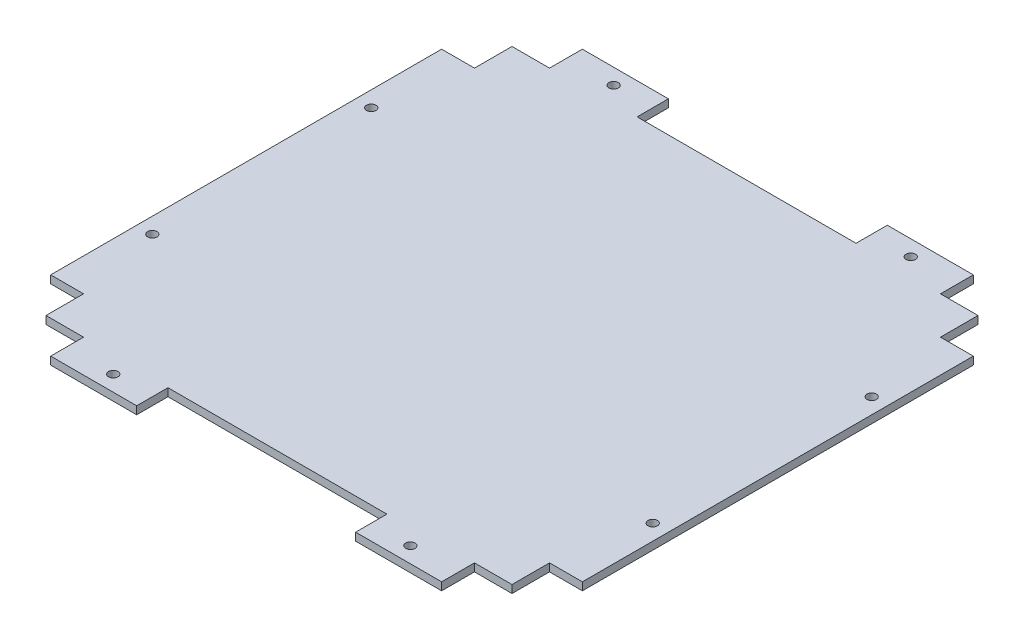
SolidWorks part; units mm, degrees
material "Acrylic (Medium-high impact)"
ref_plane "Front Plane" through (0, 0, 0) normal (0, 0, 1) x (1, 0, 0)
ref_plane "Top Plane" through (0, 0, 0) normal (0, 1, 0) x (1, 0, 0)
ref_plane "Right Plane" through (0, 0, 0) normal (1, 0, 0) x (0, 0, -1)
sketch "Sketch1" plane through (0, 0, 0) normal (0, 1, 0) x (1, 0, 0)
  line L0 (0, -45) -> (21, -45)
  line L1 (45, 0) -> (295, 0)
  line L2 (0, -45) -> (0, -295)
  line L3 (45, -340) -> (295, -340)
  line L4 (340, -45) -> (340, -295)
  line L5 (21, -45) -> (21, -21)
  line L6 (21, -21) -> (45, -21)
  line L7 (45, -21) -> (45, 0)
  line L8 (170, -340) -> (170, -241.5476) construction
  line L9 (340, -170) -> (240.7442, -170) construction
  line L10 (45, -319) -> (45, -340)
  line L11 (21, -319) -> (45, -319)
  line L12 (21, -295) -> (21, -319)
  line L13 (0, -295) -> (21, -295)
  line L14 (295, -21) -> (295, 0)
  line L15 (319, -21) -> (295, -21)
  line L16 (319, -45) -> (319, -21)
  line L17 (340, -45) -> (319, -45)
  line L18 (295, -319) -> (295, -340)
  line L19 (319, -319) -> (295, -319)
  line L20 (319, -295) -> (319, -319)
  line L21 (340, -295) -> (319, -295)
  dimension "D1" = 340
  dimension "D2" = 340
  dimension "D3" = 45
  dimension "D4" = 45
  dimension "D5" = 21
  dimension "D6" = 21
  dimension "D7" = 170
extrude "Boss-Extrude1" add sketch "Sketch1" along normal blind 5
sketch "Sketch2" plane through (0, 5, 0) normal (0, 1, 0) x (1, 0, 0)
  line L0 (45, 0) -> (45, -10) construction
  line L1 (45, 0) -> (45, -21) construction
  line L2 (45, -10) -> (295, -10) construction
  line L3 (295, -21) -> (295, 0) construction
  line L4 (0, -170) -> (142.2873, -170) construction
  line L5 (0, -45) -> (0, -295) construction
  line L6 (170, -340) -> (170, -223.8857)
  line L7 (45, -340) -> (295, -340) construction
  line L8 (21, -21) -> (138.7279, -138.7279)
  line L10 (45, -319) -> (45, -340) construction
  line L11 (295, -340) -> (295, -319) construction
  circle A0 centre (75, -10) radius 3
  circle A1 centre (265, -10) radius 3
  circle A2 centre (265, -330) radius 3
  circle A3 centre (75, -330) radius 3
  circle A4 centre (10, -240) radius 3
  circle A5 centre (10, -100) radius 3
  circle A6 centre (330, -240) radius 3
  circle A7 centre (330, -100) radius 3
  dimension "D2" = 6
  dimension "D3" = 6
  dimension "D6" = 30
  dimension "D7" = 30
  dimension "D5" = 30
  dimension "D1" = 10
  dimension "D4" = 30
extrude "Cut-Extrude1" cut sketch "Sketch2" against normal blind 57 and the other way blind 57 contours A0 | A1 | A6 | A7 | A2 | A3 | A4 | A5
sketch "Sketch3" plane through (0, 5, 0) normal (0, 1, 0) x (1, 0, 0)
  line L0 (100, 0) -> (240, 0)
  line L1 (295, 0) -> (45, 0) construction
  line L2 (100, 0) -> (100, -20)
  line L3 (100, -20) -> (240, -20)
  line L4 (240, -20) -> (240, 0)
  line L5 (295, -21) -> (295, 0) construction
  line L6 (0, -170) -> (100, -170) construction
  line L7 (0, -45) -> (0, -295) construction
  line L8 (100, -340) -> (100, -320)
  line L9 (100, -320) -> (240, -320)
  line L10 (240, -320) -> (240, -340)
  line L11 (100, -340) -> (240, -340)
  dimension "D1" = 55
  dimension "D3" = 20
  dimension "D4" = 140
extrude "Cut-Extrude2" cut sketch "Sketch3" against normal blind 10
